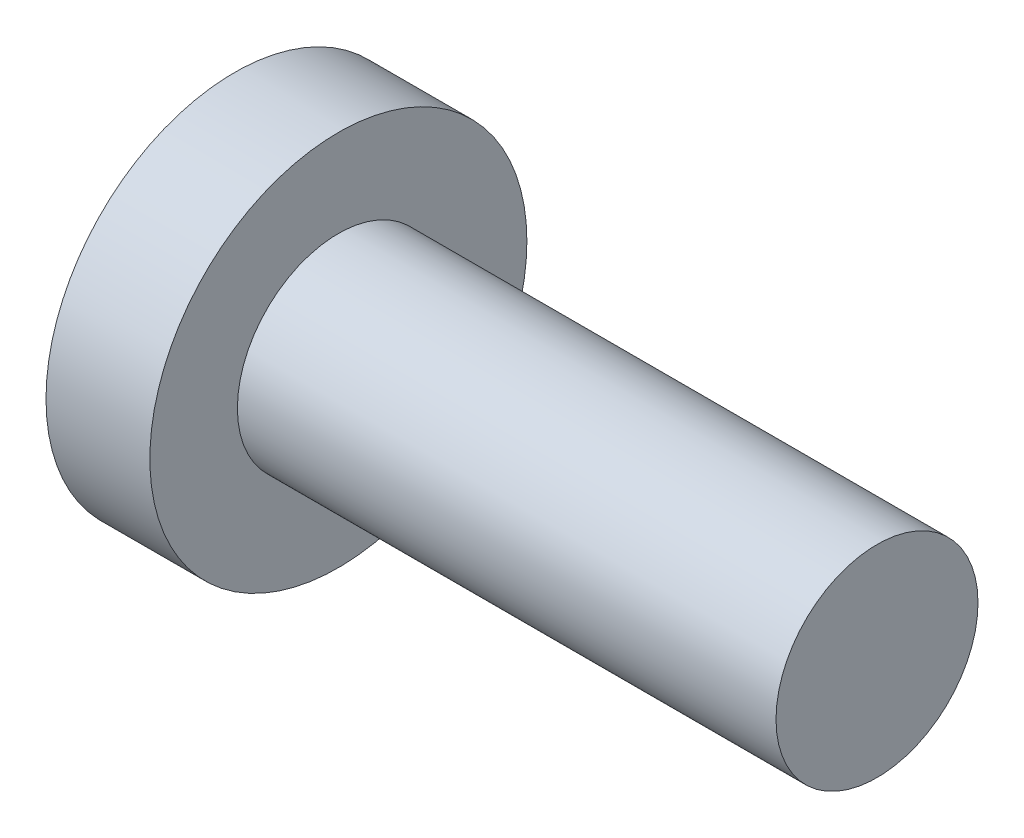
SolidWorks part; units mm, degrees
ref_plane "Front" through (0, 0, 0) normal (0, 0, 1) x (1, 0, 0)
ref_plane "Top" through (0, 0, 0) normal (0, 1, 0) x (1, 0, 0)
ref_plane "Right" through (0, 0, 0) normal (1, 0, 0) x (0, 0, -1)
sketch "Sketch1" plane through (0, 0, 0) normal (0, 0, 1) x (1, 0, 0)
  line L0 (10.4, 1.5) -> (3.4, 1.5)
  line L1 (2.4, 1.8) -> (2.4, 2.8)
  line L2 (2.4, 2.8) -> (0.8575, 2.8)
  line L3 (3.4, 1.5) -> (2.7, 1.5) construction
  line L4 (10.4, 1.5) -> (10.4, 0)
  line L5 (4.5158, 0) -> (-13.5157, 0) construction
  line L6 (10.4, 0) -> (0, 0)
  line L7 (3.4, 1.5) -> (2.4, 1.5)
  line L8 (2.4, 1.5) -> (2.4, 1.8)
  arc A0 (0.8575, 2.8) -> (0, 0) centre (5, 0) ccw
  arc A1 (2.4, 1.8) -> (2.7, 1.5) centre (2.7, 1.8) ccw construction
  dimension "r" = 0.3
  dimension "r1" = 5
  dimension "dk" = 5.6
  dimension "l" = 8
  dimension "k" = 2.4
  dimension "a" = 1
  dimension "da" = 3.6
revolve "Base" add sketch "Sketch1" angle 360 about L5
cosmetic thread "ThreadCosmetic1" [suppressed] parameters "bb"=8, "THD_MINOR"=2.459
sketch "Sketch6" plane through (0, 0, 0) normal (1, 0, 0) x (0, 0, -1)
  line L0 (-1.9271, 0) -> (2.0512, 0) construction
  line L1 (0, 1.8651) -> (0, -2.0207) construction
  line L2 (0.3, 0.3) -> (0.3, 1.5)
  line L3 (0.3, 1.5) -> (-0.3, 1.5)
  line L4 (-0.3, 0.3) -> (-0.3, 1.5)
  line L5 (0.3, 0.3) -> (1.5, 0.3)
  line L6 (1.5, 0.3) -> (1.5, -0.3)
  line L7 (-1.5, 0.3) -> (-1.5, -0.3)
  line L8 (-0.3, 0.3) -> (-1.5, 0.3)
  line L9 (-0.3, -0.3) -> (-1.5, -0.3)
  line L10 (0.3, -0.3) -> (1.5, -0.3)
  line L11 (-0.3, -0.3) -> (-0.3, -1.5)
  line L12 (0.3, -1.5) -> (-0.3, -1.5)
  line L13 (0.3, -0.3) -> (0.3, -1.5)
  point P16 (-1.5, 0)
  point P17 (1.5, 0)
extrude "CrossRecess" cut sketch "Sketch6" along normal blind 1.68
fillet "Fillet5" radius 0.3 4 edges at (0.849, -0.3, 0.3) (0.849, -0.3, -0.3) (0.849, 0.3, 0.3) (0.849, 0.3, -0.3)
draft "Draft1" type of draft neutral plane draft angle 30 neutral plane "Right" faces to draft 4 face at (0.9575, -1.5, 0) face at (0.9575, 0, -1.5) face at (0.9575, 0, 1.5) face at (0.9575, 1.5, 0) neutral plane through (0, 0, 0) neutral plane normal (1, 0, 0) reverse direction yes parameters "D1"=30
sketch "Sketch7" plane through (0, 0, 0) normal (1, 0, 0) x (0, 0, -1)
  line L0 (-2.0126, 0) -> (1.9757, 0) construction
  line L1 (0, 1.9314) -> (0, -2.0126) construction
  line L2 (0, 0) -> (1.5555, 1.5555) construction
  line L3 (0, 0.4483) -> (1.0607, 1.0607)
  line L4 (-1.5402, 1.5402) -> (0, 0) construction
  line L5 (0.4483, 0) -> (1.0607, 1.0607)
  line L6 (0, -0.4483) -> (1.0607, -1.0607)
  line L7 (0.4483, 0) -> (1.0607, -1.0607)
  line L8 (-0.4483, 0) -> (-1.0607, -1.0607)
  line L9 (0, -0.4483) -> (-1.0607, -1.0607)
  line L10 (-0.4483, 0) -> (-1.0607, 1.0607)
  line L11 (0, 0.4483) -> (-1.0607, 1.0607)
  dimension "D3" = 15
extrude "Cut-Extrude3" [suppressed] cut sketch "Sketch7" along normal blind 40.2 draft 9
sketch "Sketch8" plane through (0, 0, 0) normal (0, 0, 1) x (1, 0, 0)
  line L0 (-14.6, 1.5) -> (-15.85, 1.2295)
  line L1 (-15.85, 1.2295) -> (2.4, 1.2295)
  line L2 (10.4, -1.5) -> (10.4, 1.5) construction
  line L3 (2.4, -2.8) -> (2.4, 2.8) construction
  line L6 (2.4, 1.2295) -> (2.4, 2.8)
  line L7 (2.4, 2.8) -> (-14.6, 2.8)
  line L8 (-14.6, 2.8) -> (-14.6, 1.5)
  line L9 (73.4853, 0) -> (63.9694, 0) construction
  dimension "x" = 1.25
sketch "Sketch9" plane through (0, 0, 0) normal (0, 0, 1) x (1, 0, 0)
  line L0 (10.4, 1.2657) -> (10.5352, 1.5)
  line L1 (10.5352, 1.5) -> (10.5352, 1.7705)
  line L2 (10.5352, 1.7705) -> (10.2647, 1.7705)
  line L3 (10.2647, 1.7705) -> (10.2647, 1.5)
  line L4 (10.2647, 1.5) -> (10.4, 1.2657)
  line L5 (10.4, -1.5) -> (10.4, 1.5) construction
  line L6 (0, 0) -> (76.7811, 0) construction
  dimension "D1" = 3
  dimension "D2" = 0.2705
revolve "Cut-Revolve10" [suppressed] cut sketch "Sketch9" angle 360 about L6
pattern_linear "LPattern10" [suppressed] count 25 spacing 0.3246 along (-1, 0, 0) of bodies 105
equation "\"D1@Sketch6\" = \"m@Sketch6\" / 5"
equation "\"D1@CrossRecess\" = 0.7*\"k@Sketch1\""
equation "\"D1@Sketch9\" = \"d@Sketch1\" "
equation "\"D2@Sketch9\" =  ( \"d@Sketch1\" - \"THD_MINOR@ThreadCosmetic1\" )  / 2"
equation "\"D3@LPattern10\" =\"D2@Sketch9\" * 1.2"
equation "\"D1@LPattern10\" = \"bb@ThreadCosmetic1\" / \"D3@LPattern10\" "
